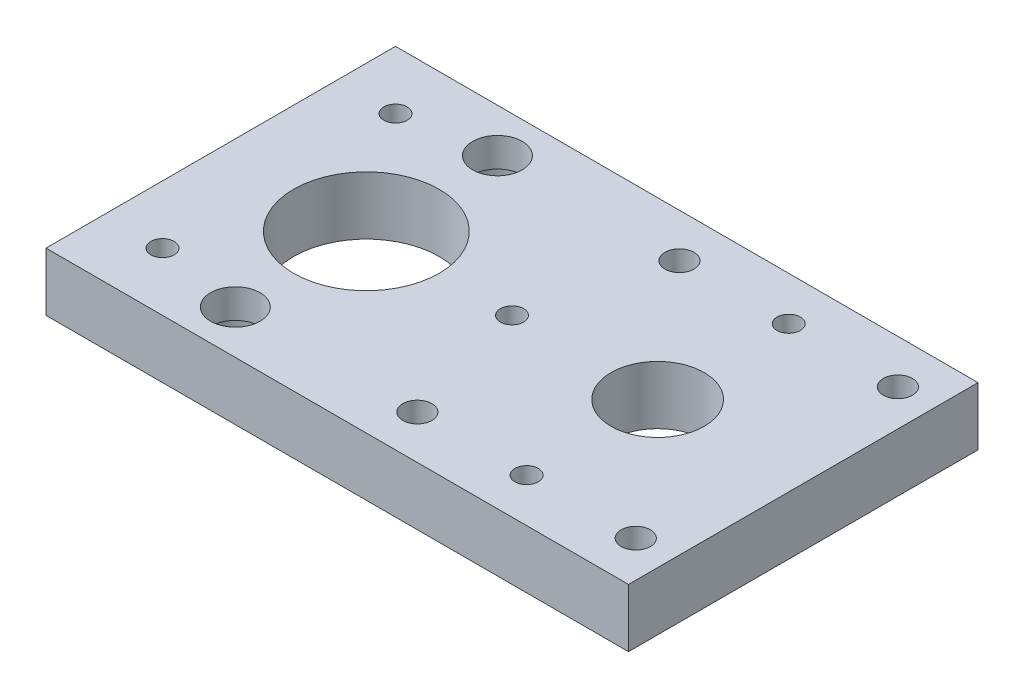
SolidWorks part; units mm, degrees
ref_plane "前视基准面" through (0, 0, 0) normal (0, 0, 1) x (1, 0, 0)
ref_plane "上视基准面" through (0, 0, 0) normal (0, 1, 0) x (1, 0, 0)
ref_plane "右视基准面" through (0, 0, 0) normal (1, 0, 0) x (0, 0, -1)
other "Configuration Table"
sketch "草图1" plane through (0, 0, 0) normal (0, 1, 0) x (1, 0, 0)
  line L0 (-5, 6) -> (-2.5, 3)
  line L1 (-5, 6) -> (5, 6)
  line L2 (-5, 6) -> (-5, -6)
  line L3 (-5, -6) -> (5, -6)
  line L4 (5, 6) -> (5, -6)
  line L5 (-5, 6) -> (5, -6) construction
  line L6 (-5, -6) -> (5, 6) construction
  line L7 (-2.5, 3) -> (2.5, 3)
  line L8 (-2.5, 3) -> (-2.5, -3)
  line L9 (-2.5, -3) -> (2.5, -3)
  line L10 (2.5, 3) -> (2.5, -3)
  line L11 (-2.5, 3) -> (2.5, -3) construction
  line L12 (-2.5, -3) -> (2.5, 3) construction
  line L13 (2.5, -3) -> (5, -6)
  line L15 (-5, 6) -> (-15, 6)
  line L16 (-5, 6) -> (-5, -6)
  line L17 (-5, -6) -> (-15, -6)
  line L18 (-15, 6) -> (-15, -6)
  circle A0 centre (0, 0) radius 1.6
  circle A1 centre (-3.75, 4.5) radius 0.5
  circle A2 centre (3.75, -4.5) radius 0.5
  circle A3 centre (3.75, 4.5) radius 0.5
  circle A4 centre (-3.75, -4.5) radius 0.5
  circle A5 centre (-3.75, 4.5) radius 1
  circle A6 centre (3.75, 4.5) radius 1
  circle A7 centre (-3.75, -4.5) radius 1
  circle A8 centre (3.75, -4.5) radius 1
  circle A9 centre (-10, 4.5) radius 0.85
  circle A10 centre (-10, -4.5) radius 0.85
  circle A11 centre (-10, -4.5) radius 1.1
  circle A12 centre (-10, 4.5) radius 1.1
  circle A13 centre (-10, 0) radius 2.5
  point P0 (0, 0)
  point P5 (0, 0)
  dimension "D1" = 3.2
  dimension "D4" = 1
  dimension "D8" = 2
  dimension "D10" = 5
  dimension "D11" = 2.2
  dimension "D12" = 1.7
  dimension "D2" = 6
  dimension "D3" = 12
  dimension "D5" = 1.5
  dimension "D6" = 1.25
  dimension "D7" = 10
  dimension "D9" = 10
extrude "凸台-拉伸1" add sketch "草图1" along normal blind 2 contours A8 L13 L9 L8 L0 A5 L2 L3 A7 | A8 L13 L4 L1 L0 A5 L7 L10 A6 | L10 L7 L8 L9 A0 | L15 L18 L17 L2 | A6 | A8 | A7 | A5 | A12 | A11 region at (0, 0, -5.8438) region at (-4.8151, 0, -5.5341) region at (-5.1562, 0, 0) region at (0, 0, -2.9219)
extrude "切除-拉伸1" cut sketch "草图1<4>" along normal through all contours A9 | A1 | A3 | A2 | A4 | A10
sketch "草图1<4>" plane through (0, 0, 0) normal (0, 1, 0) x (1, 0, 0) same geometry as "草图1"
extrude "切除-拉伸2" cut sketch "草图1<5>" along normal offset from surface (1 mm away) 1 contours A12 | A11 | A7 | A5 | A6 | A8 up to face at (-10, 2, 5.35)
sketch "草图1<5>" plane through (0, 0, 0) normal (0, 1, 0) x (1, 0, 0) same geometry as "草图1"
sketch "草图2" plane through (0, 0, 0) normal (0, -1, 0) x (1, 0, 0)
  line L0 (-15, -6) -> (-15, 6) construction
  line L1 (-15, -6) -> (5, -6) construction
  line L2 (-15, 6) -> (5, 6) construction
  circle A0 centre (-13, 4) radius 0.4
  circle A2 centre (-5, 0) radius 0.4
  circle A3 centre (-13, -4) radius 0.4
  circle A4 centre (0, -4.5) radius 0.4
  circle A5 centre (0, 4.5) radius 0.4
  dimension "D1" = 0.8
  dimension "D2" = 2
  dimension "D3" = 2
  dimension "D4" = 2
  dimension "D5" = 1.5
  dimension "D6" = 1.5
  dimension "D8" = 10
extrude "切除-拉伸3" cut sketch "草图2" against normal through all
